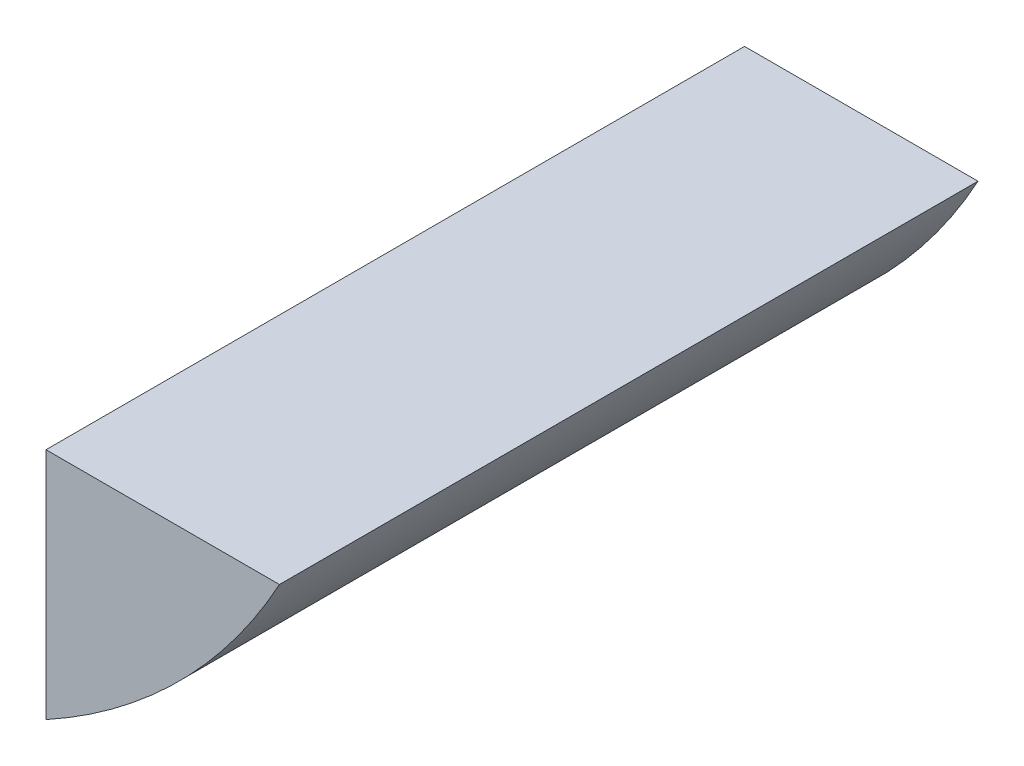
SolidWorks part; units mm, degrees
material "ABS"
ref_plane "Płaszczyzna przednia" through (0, 0, 0) normal (0, 0, 1) x (1, 0, 0)
ref_plane "Płaszczyzna górna" through (0, 0, 0) normal (0, 1, 0) x (1, 0, 0)
ref_plane "Płaszczyzna prawa" through (0, 0, 0) normal (1, 0, 0) x (0, 0, -1)
sketch "Szkic1" plane through (0, 0, 0) normal (0, 0, 1) x (1, 0, 0)
  line L4 (32.9596, -19.1815) -> (16.25, -19.1815)
  line L5 (16.25, -19.1815) -> (16.25, -35.9101)
  line L6 (32.9596, -19.1815) -> (16.25, -19.1815)
  line L7 (16.25, -19.1815) -> (16.25, -35.9101)
  arc A2 (16.25, -35.9101) -> (32.9596, -19.1815) centre (-3.9829, 1.0093) ccw
  arc A3 (16.25, -35.9101) -> (32.9596, -19.1815) centre (-3.9829, 1.0093) ccw
  dimension "D1" = 0.2
extrude "Dodanie-wyciągnięcie1" add sketch "Szkic1" along normal blind 50
